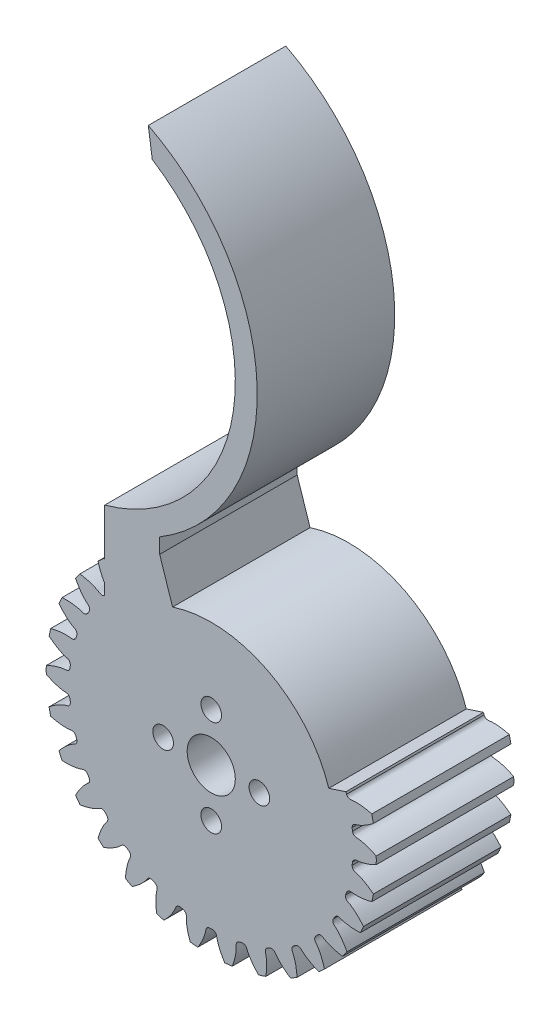
SolidWorks part; units mm, degrees
ref_plane "前视基准面" through (0, 0, 0) normal (0, 0, 1) x (1, 0, 0)
ref_plane "上视基准面" through (0, 0, 0) normal (0, 1, 0) x (1, 0, 0)
ref_plane "右视基准面" through (0, 0, 0) normal (1, 0, 0) x (0, 0, -1)
other "Configuration Table"
sketch "草图1" plane through (0, 0, 0) normal (0, 0, 1) x (1, 0, 0)
  circle A0 centre (0, 0) radius 24
extrude "凸台-拉伸1" add sketch "草图1" along normal blind 20
ref_axis "基准轴1" through (0, 0, -1.5) along (0, 0, 1)
sketch "草图2" plane through (0, 0, 0) normal (0, 0, 1) x (1, 0, 0)
  line L0 (0, 0) -> (0, 24) construction
  circle A0 centre (0, 0) radius 24 construction
  arc A1 (0.2183, 20.6238) -> (-0.2183, 20.6238) centre (0, 0) ccw
  arc A2 (5.0495, 27.2858) -> (-5.0495, 27.2858) centre (0, 0) ccw
  spline S0 degree 3 poles (0.2183, 20.6238) (0.7623, 20.7195) (0.7655, 21.0707) (0.8385, 21.4329) (0.8549, 21.5072) (0.8749, 21.5894) (0.8986, 21.6793) (0.9264, 21.7769) (0.9587, 21.8821) (0.9957, 21.9945) (1.0378, 22.1142) (1.0852, 22.241) (1.1382, 22.3746) (1.1972, 22.515) (1.2624, 22.6619) (1.3341, 22.8151) (1.4126, 22.9744) (1.4981, 23.1396) (1.591, 23.3106) (1.6914, 23.487) (1.7997, 23.6686) (1.9161, 23.8552) (2.0408, 24.0465) (2.1741, 24.2422) (2.3161, 24.4422) (2.4671, 24.6461) (2.6274, 24.8536) (2.7971, 25.0644) (2.9764, 25.2783) (3.1655, 25.4949) (3.3646, 25.714) (3.5738, 25.9352) (3.7934, 26.1582) (4.0234, 26.3827) (4.264, 26.6083) (4.6034, 26.9139) (4.868, 27.1381) (5.0495, 27.2858) knots 0 0 0 0 0.115324 0.123413 0.132512 0.142623 0.153745 0.165878 0.179022 0.193177 0.208343 0.22452 0.241708 0.259907 0.279117 0.299338 0.320571 0.342814 0.366068 0.390334 0.41561 0.441898 0.469196 0.497506 0.526827 0.557158 0.588501 0.620855 0.65422 0.688595 0.723982 0.76038 0.797789 0.836209 0.87564 0.916083 1 1 1 1
  spline S1 degree 3 poles (-0.2183, 20.6238) (-0.7623, 20.7195) (-0.7655, 21.0707) (-0.8385, 21.4329) (-0.8549, 21.5072) (-0.8749, 21.5894) (-0.8986, 21.6793) (-0.9264, 21.7769) (-0.9587, 21.8821) (-0.9957, 21.9945) (-1.0378, 22.1142) (-1.0852, 22.241) (-1.1382, 22.3746) (-1.1972, 22.515) (-1.2624, 22.6619) (-1.3341, 22.8151) (-1.4126, 22.9744) (-1.4981, 23.1396) (-1.591, 23.3106) (-1.6914, 23.487) (-1.7997, 23.6686) (-1.9161, 23.8552) (-2.0408, 24.0465) (-2.1741, 24.2422) (-2.3161, 24.4422) (-2.4671, 24.6461) (-2.6274, 24.8536) (-2.7971, 25.0644) (-2.9764, 25.2783) (-3.1655, 25.4949) (-3.3646, 25.714) (-3.5738, 25.9352) (-3.7934, 26.1582) (-4.0234, 26.3827) (-4.264, 26.6083) (-4.6034, 26.9139) (-4.868, 27.1381) (-5.0495, 27.2858) knots 0 0 0 0 0.115324 0.123413 0.132512 0.142623 0.153745 0.165878 0.179022 0.193177 0.208343 0.22452 0.241708 0.259907 0.279117 0.299338 0.320571 0.342814 0.366068 0.390334 0.41561 0.441898 0.469196 0.497506 0.526827 0.557158 0.588501 0.620855 0.65422 0.688595 0.723982 0.76038 0.797789 0.836209 0.87564 0.916083 1 1 1 1
extrude "切除-拉伸1" cut sketch "草图2" along normal through all
pattern_circular "阵列(圆周)1" count 30 every 12 about axis through (0, 0, -1.5) along (0, 0, 1) of "切除-拉伸1"
sketch "草图3" plane through (0, 0, 0) normal (0, 0, 1) x (1, 0, 0)
  circle A0 centre (0, 0) radius 22.5 construction
  dimension "Dn" = 45
sketch "草图4" plane through (0, 0, 0) normal (0, 0, -1) x (-1, 0, 0)
  circle A0 centre (0, 0) radius 15
  dimension "D1" = 30
extrude "切除-拉伸2" cut sketch "草图4" against normal blind 12
sketch "草图6" plane through (0, 0, 20) normal (0, 0, 1) x (1, 0, 0)
  line L0 (0, 0) -> (37.8831, 0) construction
  line L1 (0, 0) -> (0, 35.523) construction
  circle A0 centre (0, 0) radius 3.5
  circle A1 centre (0, 7) radius 1.5
  circle A2 centre (7, 0) radius 1.5
  circle A3 centre (0, -7) radius 1.5
  circle A4 centre (-7, 0) radius 1.5
  dimension "D1" = 7
  dimension "D2" = 3
  dimension "D3" = 3
  dimension "D4" = 7
  dimension "D5" = 7
extrude "切除-拉伸3" cut sketch "草图6" against normal blind 10
sketch "草图7" plane through (0, 0, 20) normal (0, 0, 1) x (1, 0, 0)
  line L0 (0, 0) -> (39.2254, 0) construction
  line L1 (0, 0) -> (0, 44.0708) construction
  line L2 (0, 0) -> (-30.2974, 0) construction
  line L3 (-22.5, 0) -> (-22.5, 62.8731) construction
  line L4 (-7.5, 0) -> (-7.5, 25)
  line L5 (-15.5, 0) -> (-15.5, 25)
  line L6 (-9.1555, 76) -> (-8.5803, 72)
  line L7 (-15.5, 0) -> (-7.5, 0)
  circle A0 centre (0, 0) radius 17.5 construction
  circle A1 centre (0, 0) radius 22.5 construction
  circle A2 centre (-22.5, 50.04) radius 26 construction
  circle A3 centre (-22.5, 50.04) radius 29.189 construction
  arc A4 (-15.5, 25) -> (-8.5803, 72) centre (-22.5, 50.04) ccw
  arc A5 (-7.5, 25) -> (-9.1555, 76) centre (-22.5, 50.04) ccw
  arc A7 (-15.5, 8.124) -> (-7.5, 15.8114) centre (0, 0) cw
  dimension "D1" = 35
  dimension "D2" = 45
  dimension "D7" = 52
  dimension "D8" = 47
  dimension "D3" = 25
  dimension "D4" = 25
  dimension "D5" = 15
  dimension "D6" = 8
  dimension "D9" = 51
extrude "凸台-拉伸2" add sketch "草图7" against normal blind 20 contours L5 A7 L4 A5 L6 A4 region at (-12.6201, 13.1334, 20)
sketch "草图9" plane through (0, 0, 20) normal (0, 0, 1) x (1, 0, 0)
  line L0 (0, 0) -> (-7.5, 22.798) construction
  line L1 (0, 0) -> (28.4646, 9.3642) construction
  line L2 (-7.5, 22.798) -> (-5.625, 17.0985)
  line L3 (17.0985, 5.625) -> (22.798, 7.5)
  arc A0 (-5.625, 17.0985) -> (17.0985, 5.625) centre (0, 0) cw
  arc A1 (-7.5, 22.798) -> (22.798, 7.5) centre (0, 0) cw
  dimension "D2" = 18
  dimension "D1" = 90
extrude "切除-拉伸4" cut sketch "草图9" against normal blind 20
